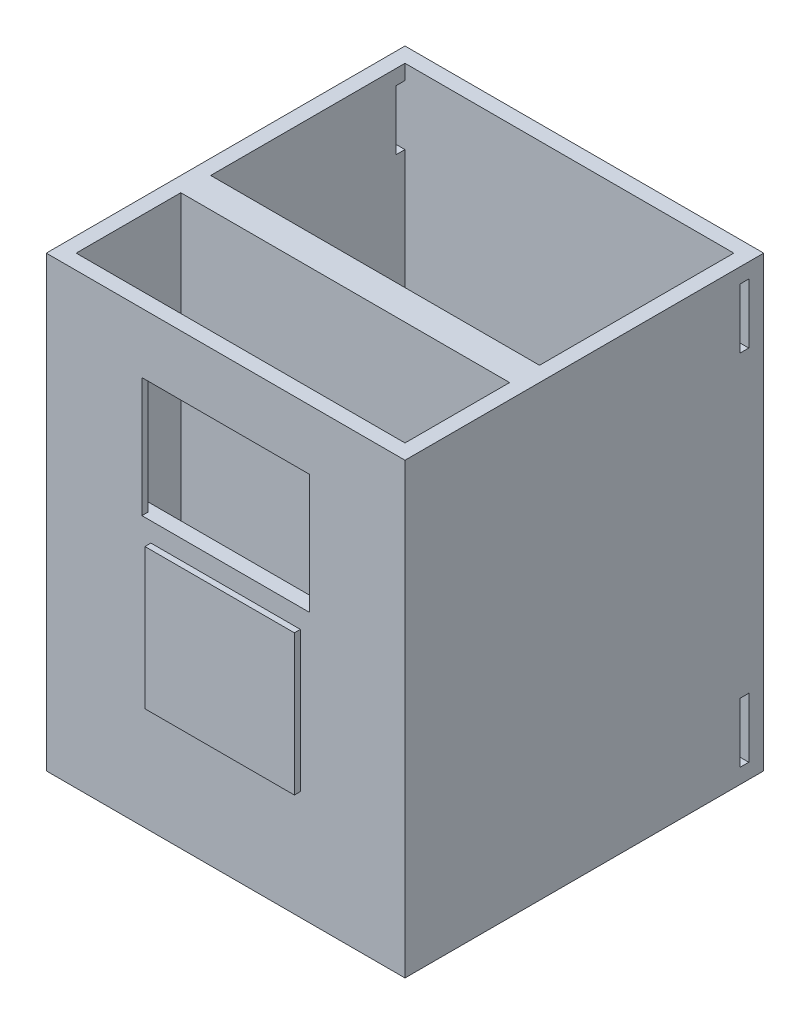
SolidWorks part; units mm, degrees
ref_plane "Front Plane" through (0, 0, 0) normal (0, 0, 1) x (1, 0, 0)
ref_plane "Top Plane" through (0, 0, 0) normal (0, 1, 0) x (1, 0, 0)
ref_plane "Right Plane" through (0, 0, 0) normal (1, 0, 0) x (0, 0, -1)
sketch "Sketch1" plane through (0, 0, 0) normal (0, 1, 0) x (1, 0, 0)
  line L1 (-60, -60) -> (60, -60)
  line L2 (-60, -60) -> (-60, 60)
  line L3 (-60, 60) -> (60, 60)
  line L4 (60, -60) -> (60, 60)
  line L5 (-60, -60) -> (60, 60) construction
  line L6 (-60, 60) -> (60, -60) construction
  point P0 (0, 0)
  dimension "D1" = 120
  dimension "D2" = 120
extrude "Boss-Extrude1" add sketch "Sketch1" along normal blind 150
sketch "Sketch2" plane through (0, 150, 0) normal (0, 1, 0) x (1, 0, 0)
  arc A0 (-60, 60) -> (60, 60) centre (0, 155.9682) ccw
shell "Shell1" thickness 5 removed face at (0, 150, 0)
sketch "Sketch3" plane through (0, 0, 0) normal (0, -1, 0) x (1, 0, 0)
  line L0 (60, 60) -> (60, -60) construction
  line L4 (-60, 60) -> (60, 60) construction
  circle A0 centre (0, 35) radius 2.5
  circle A1 centre (-5, 25) radius 1.5
  circle A2 centre (5, 25) radius 1.5
  dimension "D3" = 5
  dimension "D4" = 3
  dimension "D5" = 10
  dimension "D6" = 55
  dimension "D7" = 10
  dimension "D8" = 35
  dimension "D1" = 35
  dimension "D2" = 60
extrude "Cut-Extrude2" cut sketch "Sketch3" against normal up to next
sketch "Sketch4" plane through (0, 5, 0) normal (0, 1, 0) x (1, 0, 0)
  line L0 (-55, 55) -> (-55, -55) construction
  line L1 (-55, -20) -> (55, -20)
  line L2 (-55, -20) -> (-55, -10)
  line L3 (-55, -10) -> (55, -10)
  line L4 (55, -20) -> (55, -10)
  line L5 (55, -55) -> (55, 55) construction
  line L10 (-60, -60) -> (60, -60) construction
  dimension "D1" = 10
  dimension "D2" = 40
extrude "Boss-Extrude2" add sketch "Sketch4" along normal through all
sketch "Sketch5" plane through (0, 0, 60) normal (0, 0, 1) x (1, 0, 0)
  line L0 (60, 150) -> (60, 0) construction
  line L1 (-25, 36.5) -> (25, 36.5)
  line L2 (-25, 36.5) -> (-25, 83.5)
  line L3 (-25, 83.5) -> (25, 83.5)
  line L4 (25, 36.5) -> (25, 83.5)
  line L5 (-25, 36.5) -> (25, 83.5) construction
  line L6 (-25, 83.5) -> (25, 36.5) construction
  line L7 (-60, 150) -> (60, 150) construction
  point P0 (0, 60)
  dimension "D1" = 50
  dimension "D2" = 47
  dimension "D3" = 60
  dimension "D4" = 90
extrude "Boss-Extrude3" add sketch "Sketch5" along normal blind 2
sketch "Sketch8" plane through (0, 0, 60) normal (0, 0, 1) x (1, 0, 0)
  line L0 (-60, 150) -> (-60, 0) construction
  line L1 (-28, 89.9432) -> (28, 89.9432)
  line L2 (-28, 89.9432) -> (-28, 129.9432)
  line L3 (-28, 129.9432) -> (28, 129.9432)
  line L4 (28, 89.9432) -> (28, 129.9432)
  line L5 (-28, 89.9432) -> (28, 129.9432) construction
  line L6 (-28, 129.9432) -> (28, 89.9432) construction
  point P0 (0, 109.9432)
  dimension "D1" = 56
  dimension "D2" = 40
  dimension "D3" = 60
extrude "Cut-Extrude3" cut sketch "Sketch8" against normal up to next
sketch "Sketch9" plane through (0, 0, 55) normal (0, 0, -1) x (-1, 0, 0)
  line L17 (28, 89.9432) -> (-28, 89.9432) construction
  line L18 (-28, 129.9432) -> (-35.5, 129.9432)
  line L19 (-28, 129.9432) -> (-28, 89.9432)
  line L20 (-28, 89.9432) -> (-35.5, 89.9432)
  line L21 (-35.5, 129.9432) -> (-35.5, 89.9432)
  line L22 (-28, 89.9432) -> (-28, 129.9432) construction
  line L23 (0, 89.9432) -> (0, 129.9432) construction
  line L24 (-28, 129.9432) -> (28, 129.9432) construction
  line L25 (28, 89.9432) -> (35.5, 89.9432)
  line L26 (35.5, 129.9432) -> (35.5, 89.9432)
  line L27 (28, 129.9432) -> (35.5, 129.9432)
  line L28 (28, 129.9432) -> (28, 89.9432)
  dimension "D1" = 40
  dimension "D2" = 0
  dimension "D3" = 7.5
  dimension "D4" = 0
extrude "Cut-Extrude4" cut sketch "Sketch9" against normal offset from surface (3 mm away) 2 up to face at (0, 109.9432, 60)
sketch "Sketch10" plane through (0, 0, 62) normal (0, 0, 1) x (1, 0, 0)
  line L0 (-25, 36.5) -> (25, 36.5) construction
  line L1 (-22.5, 81) -> (22.5, 81)
  line L2 (-22.5, 81) -> (-22.5, 39)
  line L3 (-22.5, 39) -> (22.5, 39)
  line L4 (22.5, 81) -> (22.5, 39)
  line L5 (25, 36.5) -> (25, 83.5) construction
  dimension "D1" = 45
  dimension "D2" = 42
  dimension "D3" = 2.5
  dimension "D4" = 2.5
extrude "Cut-Extrude5" cut sketch "Sketch10" against normal up to next from offset 4 offset against normal yes
ref_plane "Plane1" through (0, 0, 0) normal (-1, 0, 0) x (0, 0, 1)
sketch "Sketch11" plane through (60, 0, 0) normal (1, 0, 0) x (0, 0, -1)
  line L0 (60, 150) -> (60, 0) construction
  line L1 (55, 5) -> (52, 5)
  line L2 (55, 5) -> (55, 25)
  line L3 (55, 25) -> (52, 25)
  line L4 (52, 5) -> (52, 25)
  line L5 (-60, 0) -> (60, 0) construction
  line L6 (-60, 75) -> (60, 75) construction
  line L7 (-60, 150) -> (-60, 0) construction
  line L8 (55, 125) -> (52, 125)
  line L9 (52, 145) -> (52, 125)
  line L10 (55, 145) -> (52, 145)
  line L11 (55, 145) -> (55, 125)
  dimension "D1" = 3
  dimension "D2" = 20
  dimension "D3" = 5
  dimension "D4" = 5
extrude "Cut-Extrude6" cut sketch "Sketch11" against normal up to next
mirror "Mirror1" about plane through (0, 0, 0) normal (-1, 0, 0) of "Cut-Extrude6"
